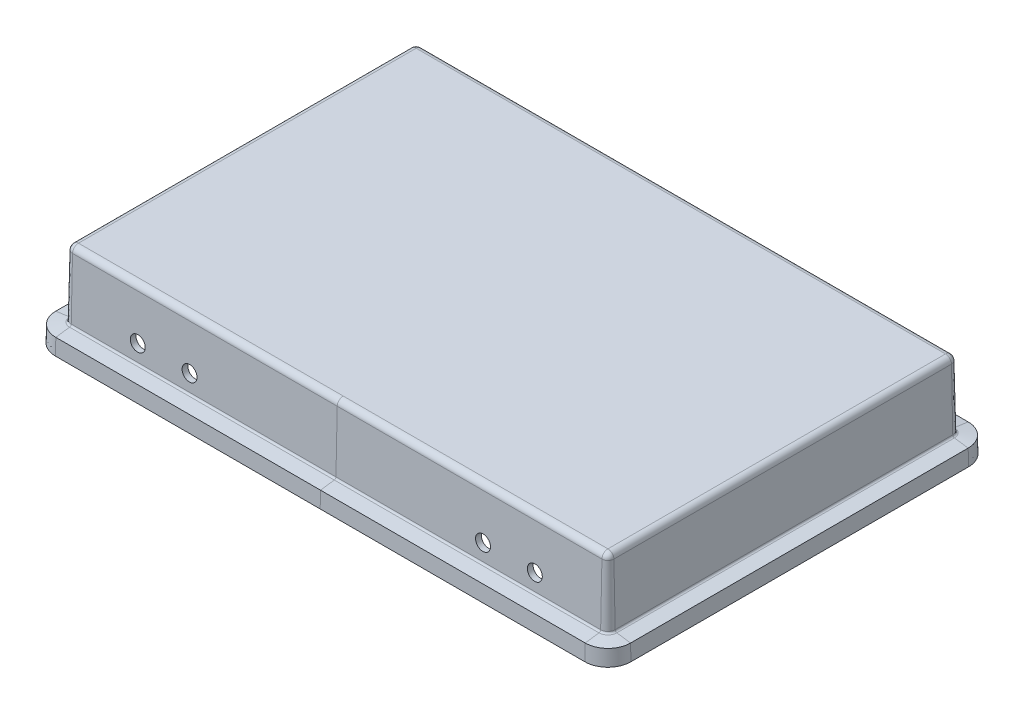
SolidWorks part; units mm, degrees
material "ABS"
ref_plane "Front Plane" through (0, 0, 0) normal (0, 0, 1) x (1, 0, 0)
ref_plane "Top Plane" through (0, 0, 0) normal (0, 1, 0) x (1, 0, 0)
ref_plane "Right Plane" through (0, 0, 0) normal (1, 0, 0) x (0, 0, -1)
sketch "MainBodyS" plane through (0, 0, 0) normal (0, 1, 0) x (1, 0, 0)
  line L1 (137.999, -88) -> (-137.999, -88)
  line L2 (138, -87.999) -> (138, 87.999)
  line L3 (137.999, 88) -> (-137.999, 88)
  line L4 (-138, -87.999) -> (-138, 87.999)
  line L5 (138, -88) -> (-138, 88) construction
  line L6 (138, 88) -> (-138, -88) construction
  arc A0 (-137.999, -88) -> (-138, -87.999) centre (-137.999, -87.999) cw
  arc A1 (137.999, -88) -> (138, -87.999) centre (137.999, -87.999) ccw
  arc A2 (138, 87.999) -> (137.999, 88) centre (137.999, 87.999) ccw
  arc A3 (-137.999, 88) -> (-138, 87.999) centre (-137.999, 87.999) ccw
  point P0 (0, 0)
  dimension "Radius" = 0.001
  dimension "Length" = 276
  dimension "Width" = 176
sketch "SideWallProfileS" plane through (0, 0, 0) normal (1, 0, 0) x (0, 0, -1)
  line L0 (-88.1227, -3.1202) -> (-89, -45)
  line L1 (-89, -45) -> (-100, -45)
  line L2 (-100, -45) -> (-99.824, -36.6)
  line L4 (-91.7834, -34.6305) -> (-91.1221, -3.0574)
  line L5 (88, 0) -> (-88, 0) construction
  line L6 (-87.999, 0) -> (-88, 0) construction
  line L7 (-88, -3) -> (-88, 0)
  line L8 (-99.824, -36.6) -> (-92.6453, -35.6)
  arc A0 (-91.1221, -3.0574) -> (-88, 0) centre (-88, -3.1228) cw
  arc A1 (-88.1227, -3.1202) -> (-88, -3) centre (-88, -3.1228) cw
  arc A2 (-92.6453, -35.6) -> (-91.7834, -34.6305) centre (-92.7832, -34.6096) ccw
  dimension "SideBaseRadius" = 1
  dimension "Thickness" = 3
  dimension "DraftAngle" = 1.2
  dimension "Height" = 45
  dimension "SideRibAngledTopHeight" = 1
  dimension "LowerBaseHeight" = 8.4
  dimension "RefHalfWidth" = 100
  dimension "BaseEdgeToInnerRadiusWidth" = 12
  dimension "ClosingBaseWidth" = 11
sweep "SideWall" add profiles "SideWallProfileS" path "MainBodyS"
sketch "TopBaseS" plane through (0, 0, 0) normal (0, 1, 0) x (1, 0, 0)
  line L4 (-138, 87.999) -> (-138, -87.999)
  line L6 (-138, 87.999) -> (-138, -87.999)
  line L12 (-137.999, -88) -> (137.999, -88)
  line L14 (-137.999, -88) -> (137.999, -88)
  line L16 (138, -87.999) -> (138, 87.999)
  line L17 (138, -87.999) -> (138, 87.999)
  line L18 (137.999, 88) -> (-137.999, 88)
  line L19 (137.999, 88) -> (-137.999, 88)
  arc A4 (-138, -87.999) -> (-137.999, -88) centre (-137.999, -87.999) ccw
  arc A5 (-138, -87.999) -> (-137.999, -88) centre (-137.999, -87.999) ccw
  arc A6 (137.999, -88) -> (138, -87.999) centre (137.999, -87.999) ccw
  arc A7 (137.999, -88) -> (138, -87.999) centre (137.999, -87.999) ccw
  arc A12 (138, 87.999) -> (137.999, 88) centre (137.999, 87.999) ccw
  arc A13 (138, 87.999) -> (137.999, 88) centre (137.999, 87.999) ccw
  arc A14 (-137.999, 88) -> (-138, 87.999) centre (-137.999, 87.999) ccw
  arc A15 (-137.999, 88) -> (-138, 87.999) centre (-137.999, 87.999) ccw
  dimension "D1" = 0
extrude "TopBase" add sketch "TopBaseS" against normal up to vertex (3 mm away) up to point (-138, -3, 87.999)
sketch "O-RingCutoutS" plane through (0, 0, 0) normal (1, 0, 0) x (0, 0, -1)
  line L0 (-97, -45) -> (-97, -41.75)
  line L1 (-100, -45) -> (-87.999, -45) construction
  line L3 (-92.5, -41.75) -> (-92.5, -45)
  line L4 (-92.5, -45) -> (-97, -45)
  line L5 (-94.75, -45) -> (-94.75, -41.75) construction
  line L6 (-94.75, -41.75) -> (-94.75, -39.5) construction
  arc A0 (-92.5, -41.75) -> (-97, -41.75) centre (-94.75, -41.75) ccw
  dimension "LowerWidth" = 4.5
  dimension "XDim" = 3
  dimension "Height" = 5.5
sketch "O-RingPathS" plane through (0, -45, 0) normal (0, -1, 0) x (1, 0, 0)
  line L0 (137.999, 89) -> (0, 89) construction
  line L1 (139, -87.999) -> (139, 87.999) construction
  line L2 (-137.999, -89) -> (137.999, -89) construction
  line L3 (-139, 87.999) -> (-139, -87.999) construction
  line L4 (0, 89) -> (-137.999, 89) construction
  line L5 (137.999, 89) -> (0, 89)
  line L6 (139, -87.999) -> (139, 87.999)
  line L7 (-137.999, -89) -> (137.999, -89)
  line L8 (-139, 87.999) -> (-139, -87.999)
  line L9 (0, 89) -> (-137.999, 89)
  arc A0 (139, 87.999) -> (137.999, 89) centre (137.999, 87.999) ccw construction
  arc A1 (137.999, -89) -> (139, -87.999) centre (137.999, -87.999) ccw construction
  arc A2 (-139, -87.999) -> (-137.999, -89) centre (-137.999, -87.999) ccw construction
  arc A3 (-137.999, 89) -> (-139, 87.999) centre (-137.999, 87.999) ccw construction
  arc A4 (139, 87.999) -> (137.999, 89) centre (137.999, 87.999) ccw
  arc A5 (137.999, -89) -> (139, -87.999) centre (137.999, -87.999) ccw
  arc A6 (-139, -87.999) -> (-137.999, -89) centre (-137.999, -87.999) ccw
  arc A7 (-137.999, 89) -> (-139, 87.999) centre (-137.999, 87.999) ccw
sweep "O-RingCutout" cut profiles "O-RingCutoutS" path "O-RingPathS"
hole_wizard "Ø7.8 (7.8) Diameter Hole1" positions "Sketch5" profile "Sketch6" hole size "Ø7.8" standard "ANSI Metric" end condition up to next
sketch "Sketch5" plane through (0, 1.9066, 91.0181) normal (0, 0.0209, 0.9998) x (1, 0, 0)
  line L0 (-103.5, -28.0844) -> (-76.5, -28.0844) construction
  line L2 (0, -47.0844) -> (-137.999, -47.0844) construction
  line L3 (-90, -28.0844) -> (-90, 0) construction
  line L4 (-90, 0) -> (0, 0) construction
  point P0 (-103.5, -28.0844)
  point P2 (-76.5, -28.0844)
  dimension "SpacingDistance" = 27
  dimension "Height" = 19
  dimension "XDim" = 90
sketch "Sketch6" plane through (-103.5, -26.1717, 91.6063) normal (1, 0, 0) x (0, -0.9998, 0.0209)
  line L0 (0, 0) -> (0, 183.3332)
  line L1 (0, 183.3332) -> (3.9, 183.3332)
  line L2 (3.9, 183.3332) -> (3.9, 0)
  line L5 (3.9, 0) -> (0, 0)
  line L11 (0, -6.35) -> (0, 107.95) construction
  dimension "Thru Hole Dia." = 7.8
  dimension "Thru Hole Depth" = 183.3332
ref_plane "LockingTabsP" through (0, -35.6, 0) normal (0, 1, 0) x (1, 0, 0)
sketch "LockingTabS" plane through (0, -35.6, 0) normal (0, 1, 0) x (1, 0, 0)
  line L0 (-137.999, 99.824) -> (137.999, 99.824) construction
  line L1 (-101.5, 96.824) -> (-78.5, 96.824)
  line L2 (-102, 97.324) -> (-102, 99.324)
  line L3 (-101.5, 99.824) -> (-78.5, 99.824)
  line L4 (-78, 97.324) -> (-78, 99.324)
  line L5 (-102, 96.824) -> (-78, 99.824) construction
  line L6 (-102, 99.824) -> (-78, 96.824) construction
  line L7 (-90, -91.6063) -> (-90, 98.324) construction
  line L8 (-103.5, -91.6063) -> (-76.5, -91.6063) construction
  arc A0 (-102, 97.324) -> (-101.5, 96.824) centre (-101.5, 97.324) ccw
  arc A1 (-78.5, 96.824) -> (-78, 97.324) centre (-78.5, 97.324) ccw
  arc A2 (-78, 99.324) -> (-78.5, 99.824) centre (-78.5, 99.324) ccw
  arc A3 (-101.5, 99.824) -> (-102, 99.324) centre (-101.5, 99.324) ccw
  point P0 (-90, 98.324)
  dimension "Radius" = 0.5
  dimension "Width" = 3
  dimension "Length" = 24
extrude "LockingTab" add sketch "LockingTabS" along normal blind 2 and the other way up to next separate body
mirror "HolesHM" about plane through (0, 0, 0) normal (1, 0, 0) of "Ø7.8 (7.8) Diameter Hole1"
mirror "LockingTabHM" about plane through (0, 0, 0) normal (1, 0, 0) of "LockingTab"
sketch "BottomCenterTabS" plane through (0, -45, 0) normal (0, -1, 0) x (1, 0, 0)
  line L0 (-12.5, -100) -> (-9.308, -106.8452)
  line L2 (-7.4954, -108) -> (7.4954, -108)
  line L3 (9.308, -106.8452) -> (12.5, -100)
  line L4 (-137.999, -100) -> (137.999, -100) construction
  line L5 (12.5, -100) -> (-12.5, -100)
  line L6 (0, -108) -> (0, -100) construction
  arc A0 (7.4954, -108) -> (9.308, -106.8452) centre (7.4954, -106) ccw
  arc A1 (-7.4954, -108) -> (-9.308, -106.8452) centre (-7.4954, -106) cw
  dimension "Radius" = 2
  dimension "Length" = 25
  dimension "Width" = 8
  dimension "Angle" = 65
sketch "TopCenterTabAngleRefS" plane through (0, 0, 0) normal (1, 0, 0) x (0, 0, -1)
  line L0 (99.8953, -40) -> (108, -41) construction
  line L1 (99.824, -36.6) -> (100, -45) construction
  line L2 (108, -45) -> (100, -45) construction
  line L3 (108, -45) -> (108, -41) construction
  dimension "YDim" = 5
  dimension "AngleHeight" = 1
sketch "TopHorzCenterTabAngleRefS" plane through (0, 2.074, -99.0139) normal (0, 0.0209, -0.9998) x (-1, 0, 0)
  line L0 (7.4954, -42.0833) -> (-7.4954, -42.0833) construction
  line L1 (7.4954, -47.2519) -> (-7.4954, -47.2519) construction
ref_plane "TopCenterTabAngleP" through (0, -27.2595, 3.3634) normal (0, -0.9925, 0.1225) x (-1, 0, 0)
sketch "TopCenterTabS" plane through (0, -27.2595, 3.3634) normal (0, -0.9925, 0.1225) x (-1, 0, 0)
  line L0 (7.5362, 111.9033) -> (-7.5362, 111.9033)
  line L1 (-12.5, 104.0417) -> (12.5, 104.0417)
  line L2 (0, 112.6977) -> (0, 104.7579) construction
  line L3 (12.5, 104.0417) -> (9.3464, 110.7538)
  line L7 (12.5, 104.7579) -> (9.308, 111.5516) construction
  line L8 (7.4954, 104.0417) -> (-7.4954, 104.0417) construction
  line L9 (0, 111.9033) -> (0, 112.2079) construction
  line L10 (-12.5, 104.0417) -> (-9.3464, 110.7538)
  arc A0 (9.3464, 110.7538) -> (7.5362, 111.9033) centre (7.5362, 109.9033) ccw
  arc A1 (-9.3464, 110.7538) -> (-7.5362, 111.9033) centre (-7.5362, 109.9033) cw
  dimension "D1" = 2
  dimension "Length" = 25
  dimension "RefDraftXDistance" = 0.3046
  dimension "DraftYDistance" = 0.3046
loft "CenterTab" add profiles "BottomCenterTabS", "TopCenterTabS" connector at (12.5, -45, -100) connector at (12.5, -40, -99.8953)
sketch "TopCenterTabCutoutS" plane through (0, -27.8048, -1.0568) normal (0, -0.9925, 0.1225) x (1, 0, 0)
  line L0 (-3.75, -99.588) -> (3.75, -99.588)
  line L1 (-7.4954, -99.588) -> (7.4954, -99.588) construction
  line L2 (3.75, -99.588) -> (3.75, -103.088)
  line L3 (-3.75, -99.588) -> (-3.75, -103.088)
  line L5 (-1.75, -105.088) -> (1.75, -105.088)
  line L6 (0, -99.588) -> (0, -107.7542) construction
  arc A0 (-3.75, -103.088) -> (-1.75, -105.088) centre (-1.75, -103.088) ccw
  arc A1 (1.75, -105.088) -> (3.75, -103.088) centre (1.75, -103.088) ccw
  point P11 (0, -105.088)
  dimension "Radius" = 2
  dimension "Width" = 7.5
  dimension "Height" = 5.5
sketch "BottomCenterTabCutoutS" plane through (0, -45, 0) normal (0, -1, 0) x (1, 0, 0)
  line L1 (-3.75, -99.8953) -> (-3.75, -103.3689) construction
  line L2 (12.5, -100) -> (-12.5, -100) construction
  line L4 (3.75, -99.8953) -> (-3.75, -99.8953)
  line L5 (3.75, -103.3689) -> (3.75, -99.8953)
  line L6 (-1.75, -105.3539) -> (1.75, -105.3539)
  line L7 (-3.75, -99.8953) -> (-3.75, -103.3689)
  line L8 (3.75, -100) -> (-3.75, -100)
  line L9 (3.75, -103.3689) -> (3.75, -100)
  line L10 (-1.75, -105.3539) -> (1.75, -105.3539)
  line L11 (-3.75, -100) -> (-3.75, -103.3689)
  ellipse E2 centre (1.75, -103.3689) end of major axis (3.75, -103.3689) minor radius 1.9849 (1.75, -105.3539) -> (3.75, -103.3689) ccw
  ellipse E3 centre (-1.75, -103.3689) end of major axis (0.25, -103.3689) minor radius 1.9849 (-3.75, -103.3689) -> (-1.75, -105.3539) ccw
  ellipse E4 centre (1.75, -103.3689) end of major axis (3.75, -103.3689) minor radius 1.9849 (1.75, -105.3539) -> (3.75, -103.3689) ccw
  ellipse E5 centre (-1.75, -103.3689) end of major axis (0.25, -103.3689) minor radius 1.9849 (-3.75, -103.3689) -> (-1.75, -105.3539) ccw
  dimension "D1" = 0
loft "CenterTabCutoutS" cut profiles "BottomCenterTabCutoutS", "TopCenterTabCutoutS" connector at (3.75, -45, -100) connector at (3.75, -40, -99.8953)
equation "\"DraftYDistance@TopCenterTabS\" = \"RefDraftXDistance@TopCenterTabS\""
